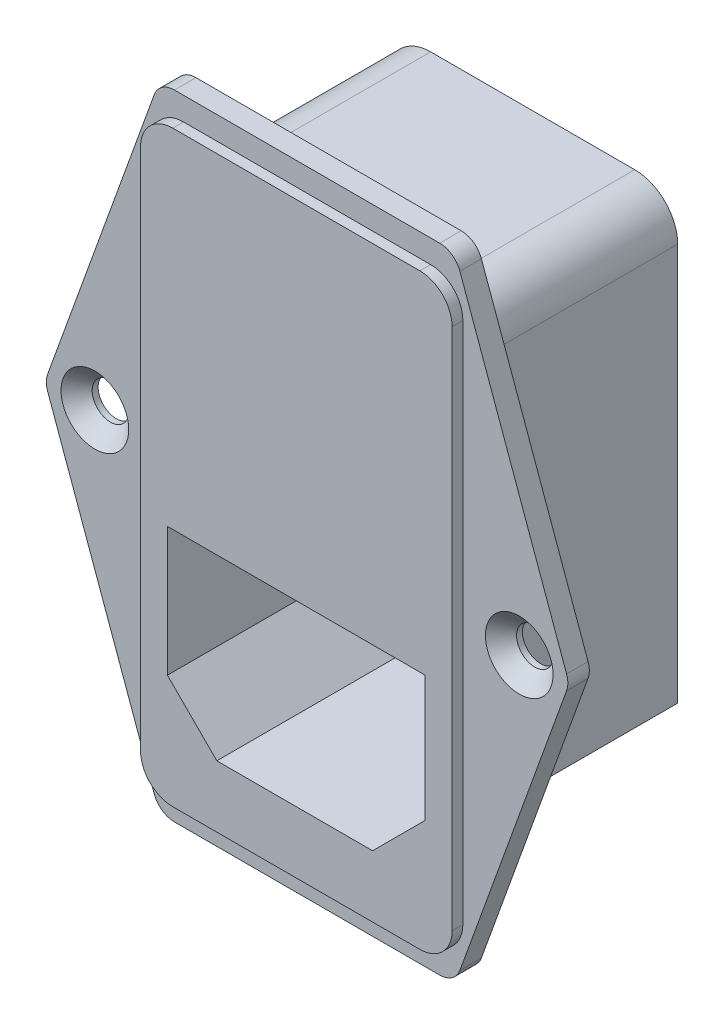
SolidWorks part; units mm, degrees
ref_plane "Front Plane" through (0, 0, 0) normal (0, 0, 1) x (1, 0, 0)
ref_plane "Top Plane" through (0, 0, 0) normal (0, 1, 0) x (1, 0, 0)
ref_plane "Right Plane" through (0, 0, 0) normal (1, 0, 0) x (0, 0, -1)
sketch "Sketch1" plane through (0, 0, 0) normal (0, 0, 1) x (1, 0, 0)
  line L0 (-13.75, 29.5) -> (-24.4, 0)
  line L1 (-13.75, -29.5) -> (13.75, -29.5)
  line L2 (-13.75, -29.5) -> (-13.75, 29.5) construction
  line L3 (-13.75, 29.5) -> (13.75, 29.5)
  line L4 (13.75, -29.5) -> (13.75, 29.5) construction
  line L5 (-13.75, -29.5) -> (13.75, 29.5) construction
  line L6 (-13.75, 29.5) -> (13.75, -29.5) construction
  line L7 (-24.4, 0) -> (-13.75, -29.5)
  line L8 (-1000, 0) -> (49000, 0) construction
  line L9 (13.75, 29.5) -> (24.4, 0)
  line L10 (24.4, 0) -> (13.75, -29.5)
  point P0 (0, 0)
  dimension "D1" = 27.5
  dimension "D2" = 59
  dimension "D3" = 24.4
  dimension "D4" = 24.4
extrude "Boss-Extrude1" add sketch "Sketch1" along normal blind 2
sketch "Sketch2" plane through (0, 0, 2) normal (0, 0, 1) x (1, 0, 0)
  line L1 (-14.5, -27.35) -> (14.5, -27.35)
  line L2 (-14.5, -27.35) -> (-14.5, 27.35)
  line L3 (-14.5, 27.35) -> (14.5, 27.35)
  line L4 (14.5, -27.35) -> (14.5, 27.35)
  line L5 (-14.5, -27.35) -> (14.5, 27.35) construction
  line L6 (-14.5, 27.35) -> (14.5, -27.35) construction
  point P0 (0, 0)
  dimension "D1" = 29
  dimension "D2" = 54.7
extrude "Boss-Extrude2" add sketch "Sketch2" along normal blind 1
fillet "Fillet1" radius 3 4 edges at (14.5, -27.35, 2.5) (-14.5, -27.35, 2.5) (14.5, 27.35, 2.5) (-14.5, 27.35, 2.5)
fillet "Fillet2" radius 2 6 edges at (-13.75, 29.5, 1) (13.75, 29.5, 1) (24.4, 0, 1) (-24.4, 0, 1) (13.75, -29.5, 1) (-13.75, -29.5, 1)
hole_wizard "CSK for M3 Flat Head Machine Screw1" positions "Sketch4" profile "Sketch3" countersink size "M3" standard "ANSI Metric" end condition through all
sketch "Sketch4" plane through (0, 0, 2) normal (0, 0, 1) x (1, 0, 0)
  line L0 (-1000, 0) -> (49000, 0) construction
  point P0 (-19.75, 0)
  point P2 (19.75, 0)
  dimension "D1" = 19.75
  dimension "D2" = 19.75
sketch "Sketch3" plane through (-19.75, 0, 2) normal (1, 0, 0) x (0, -1, 0)
  line L0 (0, 0) -> (0, 2)
  line L1 (0, 2) -> (1.7, 2)
  line L2 (1.7, 2) -> (1.7, 1.45)
  line L3 (1.7, 1.45) -> (3.15, 0)
  line L5 (3.15, 0) -> (0, 0)
  line L6 (-1.7, 1.45) -> (-3.15, 0) construction
  line L11 (0, -6.35) -> (0, 107.95) construction
  dimension "Thru Hole Dia." = 3.4
  dimension "Thru Hole Depth" = 2
  dimension "Near C'Sink Dia." = 6.3
  dimension "Near C'Sink Angle" = 90
sketch "Sketch5" plane through (0, 0, 0) normal (0, 0, -1) x (-1, 0, 0)
  line L1 (-13.5, -23.5) -> (13.5, -23.5)
  line L2 (-13.5, -23.5) -> (-13.5, 23.5)
  line L3 (-13.5, 23.5) -> (13.5, 23.5)
  line L4 (13.5, -23.5) -> (13.5, 23.5)
  line L5 (-13.5, -23.5) -> (13.5, 23.5) construction
  line L6 (-13.5, 23.5) -> (13.5, -23.5) construction
  point P0 (0, 0)
  dimension "D1" = 27
  dimension "D2" = 47
extrude "Boss-Extrude3" add sketch "Sketch5" along normal blind 19
chamfer "Chamfer1" distance 6 angle 45 2 edges at (-13.5, -23.5, -9.5) (13.5, -23.5, -9.5)
fillet "Fillet3" radius 4 2 edges at (-13.5, 23.5, -9.5) (13.5, 23.5, -9.5)
sketch "Sketch6" plane through (0, 0, 3) normal (0, 0, 1) x (1, 0, 0)
  line L0 (-12, -5) -> (12, -5)
  line L1 (12, -5) -> (12, -16.7)
  line L2 (12, -16.7) -> (7.1, -21.6)
  line L3 (7.1, -21.6) -> (-7.4, -21.6)
  line L4 (-7.4, -21.6) -> (-12, -17)
  line L5 (-12, -17) -> (-12, -5)
  dimension "D1" = 5
  dimension "D2" = 12
  dimension "D3" = 12
  dimension "D4" = 16.6
  dimension "D5" = 135
  dimension "D6" = 135
  dimension "D7" = 14.5
  dimension "D8" = 12
extrude "Cut-Extrude1" cut sketch "Sketch6" against normal blind 17
